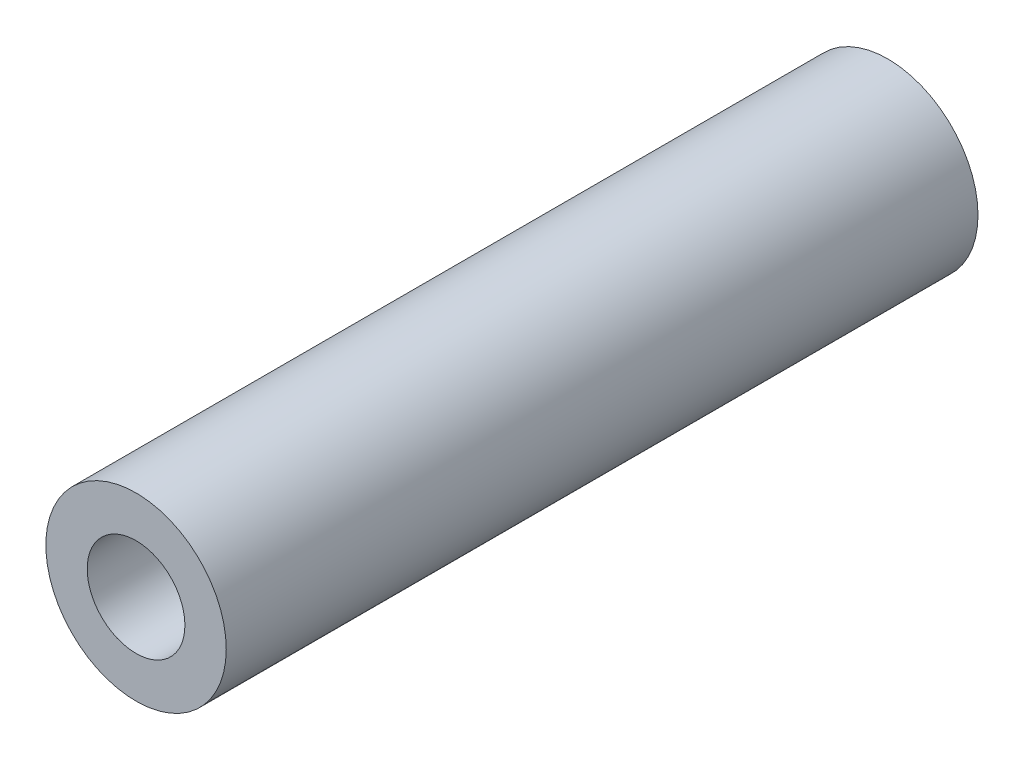
SolidWorks part; units mm, degrees
ref_plane "Front Plane" through (0, 0, 0) normal (0, 0, 1) x (1, 0, 0)
ref_plane "Top Plane" through (0, 0, 0) normal (0, 1, 0) x (1, 0, 0)
ref_plane "Right Plane" through (0, 0, 0) normal (1, 0, 0) x (0, 0, -1)
sketch "Sketch1" plane through (0, 0, 0) normal (0, 0, 1) x (1, 0, 0)
  circle A0 centre (0, 0) radius 2.4
  dimension "D1" = 4.8
extrude "Boss-Extrude1" add sketch "Sketch1" along normal blind 20 contours A0
sketch "Sketch2" plane through (0, 0, 20) normal (0, 0, 1) x (1, 0, 0)
  circle A0 centre (0, 0) radius 1.3
  dimension "D1" = 2.6
extrude "Cut-Extrude1" cut sketch "Sketch2" against normal blind 2.5
